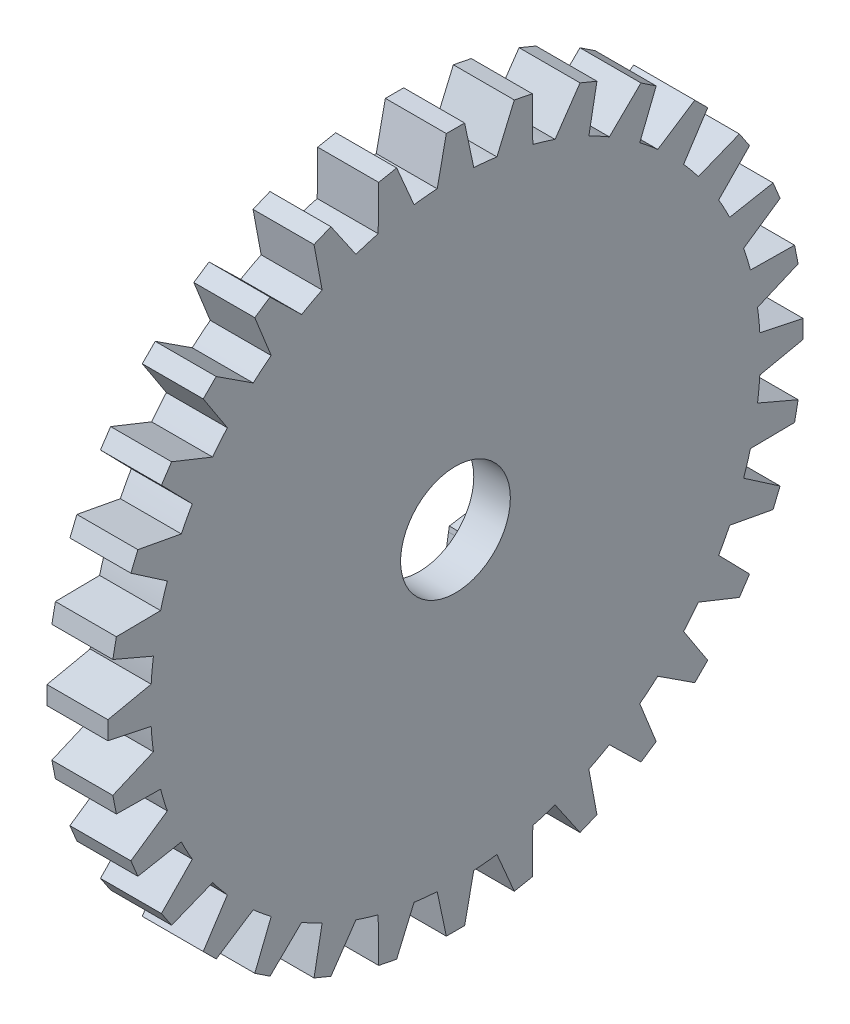
SolidWorks part; units mm, degrees
ref_plane "Front" through (0, 0, 0) normal (0, 0, 1) x (1, 0, 0)
ref_plane "Top" through (0, 0, 0) normal (0, 1, 0) x (1, 0, 0)
ref_plane "Right" through (0, 0, 0) normal (1, 0, 0) x (0, 0, -1)
sketch "Sketch1" plane through (0, 0, 0) normal (1, 0, 0) x (0, 0, -1)
  circle A0 centre (0, 0) radius 25
  dimension "D1" = 50
extrude "Boss-Extrude1" add sketch "Sketch1" along normal blind 5
sketch "Sketch3" plane through (5, 0, 0) normal (1, 0, 0) x (0, 0, -1)
  line L0 (0, 25) -> (0, 28.5) construction
  line L1 (0.75, 28.5) -> (-0.75, 28.5)
  line L2 (-0.75, 28.5) -> (-1.5, 24.955)
  line L5 (0.75, 28.5) -> (1.5, 24.955)
  line L6 (-1.5, 24.955) -> (1.5, 24.955)
  circle A0 centre (0, 0) radius 25 construction
  dimension "D1" = 3.5
  dimension "D2" = 1.5
  dimension "D3" = 3
extrude "Boss-Extrude2" add sketch "Sketch3" against normal up to surface (5 mm away) up to face at (0, 0, -25)
sketch "Sketch4" plane through (0, 0, 0) normal (0, 1, 0) x (1, 0, 0)
  line L0 (0, 0) -> (20, 0) construction
  dimension "D1" = 20
pattern_circular "CirPattern1" count 32 over 360 about axis through (0, 0, 0) along (1, 0, 0) of "Boss-Extrude2"
sketch "Sketch5" plane through (5, 0, 0) normal (1, 0, 0) x (0, 0, -1)
  circle A0 centre (0, 0) radius 4.5
  dimension "D1" = 9
extrude "Cut-Extrude1" cut sketch "Sketch5" against normal up to next
sketch "Sketch6" plane through (0, 0, 0) normal (-1, 0, 0) x (0, 0, 1)
  line L0 (0, 0) -> (0, 4.5) construction
  line L1 (0, 0) -> (3.182, 3.182) construction
  circle A0 centre (0, 16) radius 0.75
  circle A1 centre (-16, 0) radius 0.75
  circle A2 centre (0, 0) radius 4.5 construction
  circle A3 centre (0, -16) radius 0.75
  circle A4 centre (16, 0) radius 0.75
  dimension "D3" = 1.5
  dimension "D1" = 16
  dimension "D2" = 16
  dimension "D4" = 45
extrude "Cut-Extrude2" cut sketch "Sketch6" against normal offset from surface (4 mm away) 1 up to face at (5, 0, -4.5)
sketch "Sketch7" plane through (0, 0, 0) normal (-1, 0, 0) x (0, 0, 1)
  line L0 (-2.5, 17) -> (-4.43, 4.8841)
  line L1 (0, 17) -> (0, 0) construction
  line L2 (2.5, 17) -> (4.43, 4.8841)
  line L3 (17, 2.5) -> (4.4914, 4.4926)
  line L4 (17, -2.5) -> (4.8841, -4.43)
  line L5 (2.5, -17) -> (4.43, -4.8841)
  line L6 (-2.5, -17) -> (-4.43, -4.8841)
  line L7 (-17, -2.5) -> (-4.4914, -4.4926)
  line L8 (-17, 2.5) -> (-4.4914, 4.4926)
  line L9 (0, 0) -> (4.43, 4.8841) construction
  line L10 (-4.43, 4.8841) -> (-4.4914, 4.4926)
  line L11 (4.43, 4.8841) -> (4.4914, 4.4926)
  line L12 (0, 0) -> (4.5, 0) construction
  line L13 (4.43, -4.8841) -> (4.4914, -4.4926)
  line L14 (-4.43, -4.8841) -> (-4.4914, -4.4926)
  line L15 (4.8841, -4.43) -> (4.4914, -4.4926)
  arc A0 (2.5, 17) -> (-2.5, 17) centre (0, 17) ccw
  arc A1 (17, -2.5) -> (17, 2.5) centre (17, 0) ccw
  arc A2 (-2.5, -17) -> (2.5, -17) centre (0, -17) ccw
  arc A3 (-17, 2.5) -> (-17, -2.5) centre (-17, 0) ccw
  circle A4 centre (0, 0) radius 4.5 construction
  dimension "D1" = 5
  dimension "D2" = 17
  dimension "D3" = 4.43
  dimension "D5" = 6.5939
  dimension "D4" = 4
extrude "Cut-Extrude3" cut sketch "Sketch7" against normal blind 2
